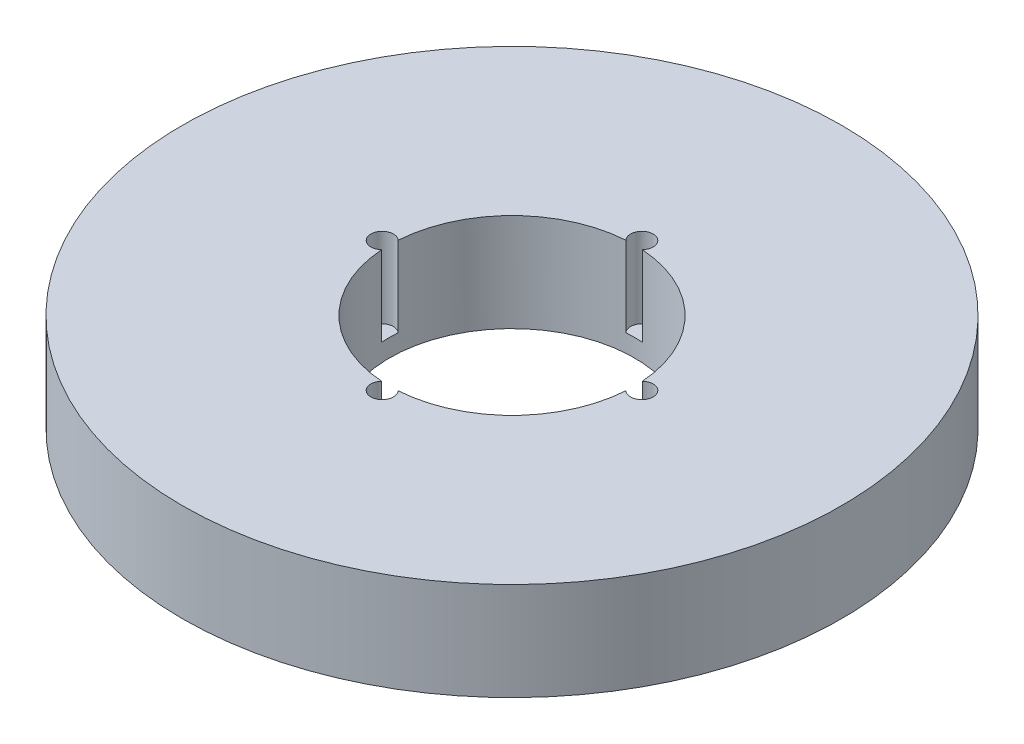
SolidWorks part; units mm, degrees
ref_plane "Front Plane" through (0, 0, 0) normal (0, 0, 1) x (1, 0, 0)
ref_plane "Top Plane" through (0, 0, 0) normal (0, 1, 0) x (1, 0, 0)
ref_plane "Right Plane" through (0, 0, 0) normal (1, 0, 0) x (0, 0, -1)
sketch "Sketch1" plane through (0, 0, 0) normal (0, 1, 0) x (1, 0, 0)
  circle A0 centre (0, 0) radius 87.5
  dimension "FLANGE_OD" = 175
extrude "Boss-Extrude1" add sketch "Sketch1" along normal blind 26
sketch "Sketch2" plane through (0, 0, 0) normal (0, 1, 0) x (1, 0, 0)
  circle A0 centre (0, 0) radius 32.5
  dimension "BORE_D" = 65
extrude "Cut-Extrude1" cut sketch "Sketch2" along normal through all
sketch "Sketch3" plane through (0, 26, 0) normal (0, 1, 0) x (1, 0, 0)
  circle A0 centre (0, 0) radius 34.4771 construction
  circle A1 centre (-34.4771, 0) radius 2.9948
  dimension "BOLT_D" = 5.9895
  dimension "BOLT_PCD" = 68.9541
extrude "Cut-Extrude2" cut sketch "Sketch3" against normal blind 21.2824
pattern_circular "CirPattern1" count 4 over 360 about axis through (0, 0, 0) along (0, 1, 0) of "Cut-Extrude2"
